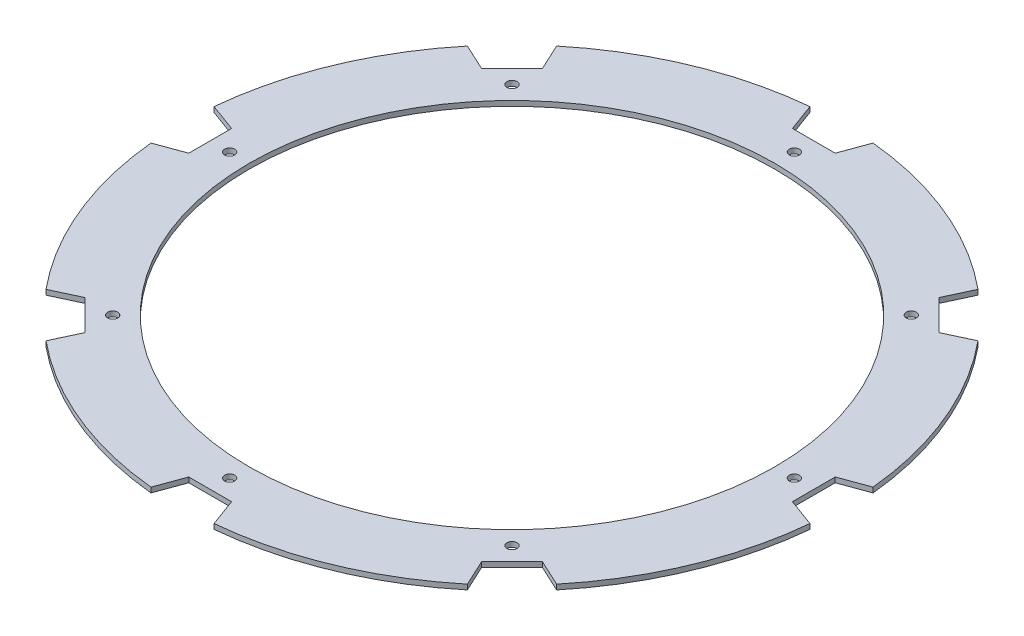
SolidWorks part; units mm, degrees
ref_plane "Front Plane" through (0, 0, 0) normal (0, 0, 1) x (1, 0, 0)
ref_plane "Top Plane" through (0, 0, 0) normal (0, 1, 0) x (1, 0, 0)
ref_plane "Right Plane" through (0, 0, 0) normal (1, 0, 0) x (0, 0, -1)
sketch "Sketch2" plane through (0, 0, 0) normal (0, 1, 0) x (1, 0, 0)
  line L0 (-215.9, 0) -> (-171.45, 0) construction
  line L1 (-171.45, 0) -> (0, 0) construction
  line L2 (0, 0) -> (171.45, 0) construction
  line L3 (171.45, 0) -> (215.9, 0) construction
  line L4 (-214.9183, 20.5652) -> (-196.85, 13.97)
  line L5 (-196.85, 13.97) -> (-196.85, -13.97)
  line L6 (-196.85, -13.97) -> (-214.9175, -20.574)
  circle A0 centre (0, 0) radius 171.45
  circle A1 centre (0, 0) radius 215.9
  circle A2 centre (-184.15, 0) radius 3.302
  point P10 (-196.85, 0)
  point P13 (-196.85, 0)
  point P15 (-171.45, 0)
  dimension "D1" = 342.9
  dimension "D2" = 431.8
  dimension "D7" = 6.604
  dimension "D3" = 27.94
  dimension "D4" = 6.5952
  dimension "D5" = 6.604
  dimension "D6" = 25.4
  dimension "D8" = 12.7
extrude "Boss-Extrude1" add sketch "Sketch2" along normal blind 3.302 contours L6 A1 L4 L5 A2 A0 region at (10.0035, 0, -209.5617)
pattern_circular "CirPattern1" count 8 over 360 about axis through (0, 3.302, 0) along (0, -1, 0) reverse direction yes of face at (-184.15, 3.302, 3.302) of face at (-196.85, 1.651, 0) of face at (-205.8837, 1.651, 17.272) of face at (-205.8842, 1.651, -17.2676)
sketch "Sketch3" plane through (0, 3.302, 0) normal (0, 1, 0) x (1, 0, 0)
  line L0 (-196.85, 13.97) -> (-196.85, -13.97) construction
  line L1 (0, 0) -> (-171.45, 0) construction
  line L2 (-171.45, 0) -> (-196.85, 0) construction
  line L3 (-196.85, 0) -> (-228.5886, 0) construction
  circle A0 centre (0, 0) radius 171.45 construction
  point P0 (-196.85, 0)
  point P1 (0, 0)
  point P4 (-171.45, 0)
